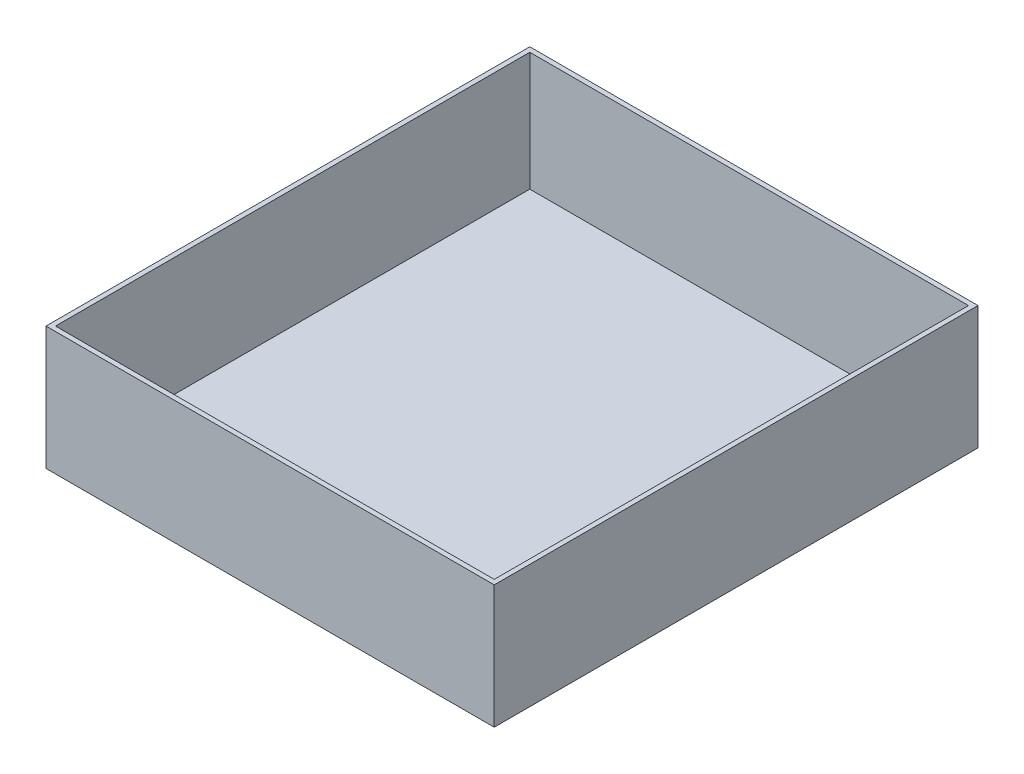
SolidWorks part; units mm, degrees
material "ABS"
ref_plane "Front Plane" through (0, 0, 0) normal (0, 0, 1) x (1, 0, 0)
ref_plane "Top Plane" through (0, 0, 0) normal (0, 1, 0) x (1, 0, 0)
ref_plane "Right Plane" through (0, 0, 0) normal (1, 0, 0) x (0, 0, -1)
sketch "Sketch2" plane through (0, 0, 0) normal (0, 1, 0) x (1, 0, 0)
  line L0 (-94.5, 102) -> (-94.5, -102)
  line L1 (-92.5, 100) -> (92.5, 100)
  line L2 (-92.5, 100) -> (-92.5, -100)
  line L3 (-92.5, -100) -> (92.5, -100)
  line L4 (92.5, 100) -> (92.5, -100)
  line L5 (-92.5, 100) -> (92.5, -100) construction
  line L6 (-92.5, -100) -> (92.5, 100) construction
  line L7 (-94.5, -102) -> (94.5, -102)
  line L8 (94.5, 102) -> (94.5, -102)
  line L9 (-94.5, 102) -> (94.5, 102)
  point P0 (0, 0)
  dimension "D1" = 200
  dimension "D2" = 185
  dimension "D3" = 2
extrude "Walls" add sketch "Sketch2" along normal blind 50
sketch "Sketch3" plane through (0, 0, 0) normal (0, -1, 0) x (1, 0, 0)
  line L1 (-94.5, -102) -> (94.5, -102)
  line L2 (-94.5, -102) -> (-94.5, 102)
  line L3 (-94.5, 102) -> (94.5, 102)
  line L4 (94.5, -102) -> (94.5, 102)
  line L5 (-94.5, -102) -> (94.5, 102) construction
  line L6 (-94.5, 102) -> (94.5, -102) construction
  point P0 (0, 0)
extrude "Base" add sketch "Sketch3" along normal blind 2
